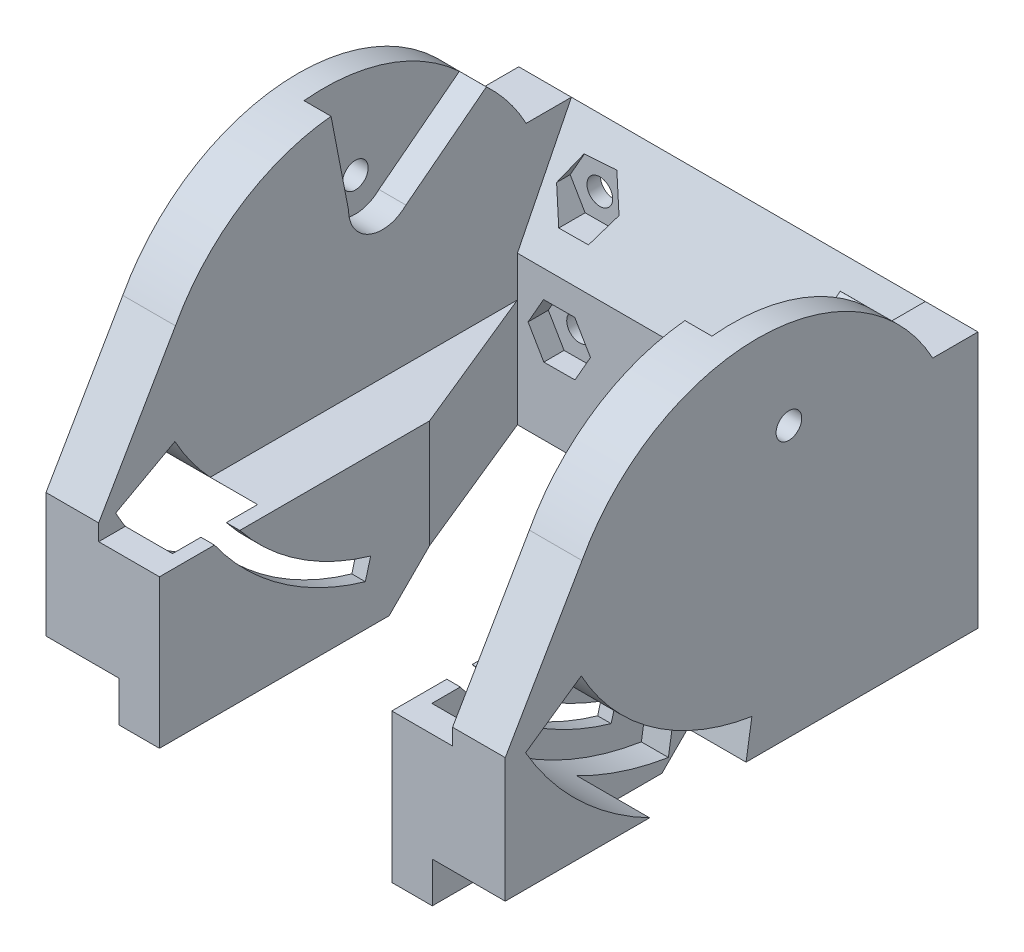
SolidWorks part; units mm, degrees
ref_plane "Alzado" through (0, 0, 0) normal (0, 0, 1) x (1, 0, 0)
ref_plane "Planta" through (0, 0, 0) normal (0, 1, 0) x (1, 0, 0)
ref_plane "Vista lateral" through (0, 0, 0) normal (1, 0, 0) x (0, 0, -1)
sketch "Croquis1" plane through (0, 0, 0) normal (0, 0, 1) x (1, 0, 0)
  line L1 (-48.8873, 14.6225) -> (-14.8873, 14.6225)
  line L2 (-48.8873, 14.6225) -> (-48.8873, -4.3775)
  line L3 (-48.8873, -4.3775) -> (-14.8873, -4.3775)
  line L4 (-14.8873, 14.6225) -> (-14.8873, -4.3775)
  dimension "D1" = 19
  dimension "D2" = 34
extrude "Saliente-Extruir1" add sketch "Croquis1" along normal blind 35
sketch "Croquis2" plane through (0, -4.3775, 0) normal (0, -1, 0) x (1, 0, 0)
  line L0 (-48.8873, 35) -> (-14.8873, 35) construction
  line L1 (-44.9873, 35) -> (-18.7873, 35)
  line L2 (-44.9873, 35) -> (-44.9873, 4)
  line L3 (-44.9873, 4) -> (-18.7873, 4)
  line L4 (-18.7873, 35) -> (-18.7873, 4)
  line L5 (-48.8873, 35) -> (-48.8873, 0) construction
  line L6 (-14.8873, 35) -> (-14.8873, 0) construction
  line L7 (-48.8873, 0) -> (-14.8873, 0) construction
  dimension "D1" = 3.9
  dimension "D2" = 3.9
  dimension "D3" = 26.2
  dimension "D4" = 4
extrude "Cortar-Extruir1" cut sketch "Croquis2" against normal blind 25
sketch "Croquis4" plane through (-18.7873, 0, 0) normal (-1, 0, 0) x (0, 0, 1)
  line L0 (4, 14.6225) -> (4, 6.6225)
  line L1 (4, 14.6225) -> (4, -4.3775) construction
  line L2 (4, 6.6225) -> (0, 14.6225)
  line L3 (0, 14.6225) -> (4, 14.6225)
extrude "Cortar-Extruir3" cut sketch "Croquis4" along normal up to vertex (26.2 mm away) up to point (-44.9873, 14.6225, 4)
sketch "Croquis9" plane through (-14.8873, 0, 0) normal (1, 0, 0) x (0, 0, -1)
  line L0 (-35, 14.6225) -> (0, 14.6225) construction
  line L1 (-29.3158, 14.6225) -> (-3.3495, 14.6225)
  line L7 (-35, -4.3775) -> (0, -4.3775) construction
  arc A0 (-29.3158, 14.6225) -> (-3.3495, 14.6225) centre (-16.3327, 7.6225) cw
  dimension "D2" = 12
extrude "Saliente-Extruir2" add sketch "Croquis9" against normal up to vertex (34 mm away) up to point (-48.8873, 14.6225, 35)
sketch "Croquis10" plane through (0, 14.6225, 0) normal (0, -1, 0) x (1, 0, 0)
  line L1 (-44.9873, 29.3158) -> (-18.7873, 29.3158)
  line L2 (-44.9873, 29.3158) -> (-44.9873, 3.3495)
  line L3 (-44.9873, 3.3495) -> (-18.7873, 3.3495)
  line L4 (-18.7873, 29.3158) -> (-18.7873, 3.3495)
extrude "Cortar-Extruir4" cut sketch "Croquis10" against normal blind 10
sketch "Croquis18" plane through (0, 0, 0) normal (0, 0, -1) x (-1, 0, 0)
  line L0 (48.8873, -4.3775) -> (14.8873, -4.3775) construction
  line L2 (48.8873, 14.6225) -> (48.8873, -4.3775) construction
  circle A0 centre (41.8873, 2.6225) radius 0.95
  circle A1 centre (21.8873, 2.6225) radius 0.95
  circle A2 centre (21.8873, 10.6225) radius 0.95
  circle A3 centre (41.8873, 10.6225) radius 0.95
  dimension "D1" = 7
  dimension "D2" = 7
  dimension "D3" = 2
  dimension "D4" = 2
extrude "Cortar-Extruir11" cut sketch "Croquis18" against normal up to vertex (4 mm away) up to point (-18.7873, -4.3775, 4)
sketch "Croquis19" plane through (0, 0, 4) normal (0, 0, 1) x (1, 0, 0)
  line L0 (-43.0308, 0.6161) -> (-40.7214, 0.629)
  line L1 (-23.0308, 0.6161) -> (-20.7214, 0.629)
  line L2 (-20.7214, 0.629) -> (-19.5779, 2.6355)
  line L3 (-19.5779, 2.6355) -> (-20.7438, 4.629)
  line L4 (-20.7438, 4.629) -> (-23.0531, 4.6161)
  line L5 (-23.0531, 4.6161) -> (-24.1966, 2.6096)
  line L6 (-24.1966, 2.6096) -> (-23.0308, 0.6161)
  line L7 (-40.7214, 0.629) -> (-39.5779, 2.6355)
  line L8 (-39.5779, 2.6355) -> (-40.7438, 4.629)
  line L9 (-40.7438, 4.629) -> (-43.0531, 4.6161)
  line L10 (-43.0531, 4.6161) -> (-44.1966, 2.6096)
  line L11 (-44.1966, 2.6096) -> (-43.0308, 0.6161)
  circle A0 centre (-21.8873, 2.6225) radius 2 construction
  circle A1 centre (-41.8873, 2.6225) radius 2 construction
  dimension "D1" = 4
  dimension "D2" = 2
extrude "Cortar-Extruir12" cut sketch "Croquis19" against normal blind 1.5
sketch "Croquis20" plane through (0, 0, 4) normal (0, 0, 1) x (1, 0, 0)
  line L12 (-44.0812, 10.6103) -> (-42.9736, 8.7165)
  line L13 (-42.9736, 8.7165) -> (-40.7797, 8.7287)
  line L14 (-40.7797, 8.7287) -> (-39.5207, 10.7358)
  line L15 (-39.5207, 10.7358) -> (-40.6283, 12.6296)
  line L16 (-40.6283, 12.6296) -> (-42.9948, 12.5164)
  line L17 (-42.9948, 12.5164) -> (-44.0812, 10.6103)
  line L18 (-24.0812, 10.6103) -> (-22.9736, 8.7165)
  line L19 (-22.9736, 8.7165) -> (-20.7797, 8.7287)
  line L20 (-20.7797, 8.7287) -> (-19.5207, 10.7358)
  line L21 (-19.5207, 10.7358) -> (-20.6283, 12.6296)
  line L22 (-20.6283, 12.6296) -> (-22.9948, 12.5164)
  line L23 (-22.9948, 12.5164) -> (-24.0812, 10.6103)
  circle A2 centre (-41.8873, 10.6225) radius 1.9 construction
  circle A3 centre (-21.8873, 10.6225) radius 1.9 construction
  dimension "D1" = 4
  dimension "D2" = 4
extrude "Cortar-Extruir13" cut sketch "Croquis20" against normal blind 3
sketch "Croquis21" plane through (-14.8873, 0, 0) normal (1, 0, 0) x (0, 0, -1)
  line L0 (0, -4.3775) -> (0, 14.6225) construction
  line L2 (-35, -4.3775) -> (0, -4.3775) construction
  circle A0 centre (-14, 15.6225) radius 0.95
  dimension "D1" = 14
  dimension "D2" = 20
extrude "Cortar-Extruir14" cut sketch "Croquis21" against normal up to vertex (34 mm away) up to point (-48.8873, 14.6225, 3.3495)
sketch "Croquis23" plane through (0, -4.3775, 0) normal (0, -1, 0) x (1, 0, 0)
  line L0 (-44.9873, 35) -> (-40.4873, 35)
  line L1 (-40.4873, 35) -> (-40.4873, 15)
  line L2 (-40.4873, 15) -> (-44.9873, 4)
  line L3 (-44.9873, 35) -> (-44.9873, 4) construction
  line L4 (-44.9873, 4) -> (-44.9873, 35)
  line L5 (-18.7873, 35) -> (-23.2873, 35)
  line L6 (-23.2873, 35) -> (-23.2873, 15)
  line L7 (-23.2873, 15) -> (-18.7873, 4)
  line L8 (-18.7873, 4) -> (-18.7873, 35)
extrude "Saliente-Extruir3" add sketch "Croquis23" against normal blind 8
sketch "Croquis24" plane through (-14.8873, 0, 0) normal (1, 0, 0) x (0, 0, -1)
  line L5 (-19.3648, -2.8648) -> (-19.7593, -4.312)
  line L6 (-30.433, 5.5966) -> (-31.6653, 4.7372)
  arc A0 (-19.3648, -2.8648) -> (-30.433, 5.5966) centre (-14, 15.6225) cw
  arc A1 (-31.6653, 4.7372) -> (-19.7593, -4.312) centre (-14, 15.6225) ccw
  dimension "D1" = 1.5
  dimension "D2" = 19.25
  dimension "D3" = 20.7498
extrude "Cortar-Extruir16" cut sketch "Croquis24" against normal up to vertex (34 mm away) up to point (-48.8873, -4.3775, 35)
sketch "Croquis25" plane through (0, -4.3775, 0) normal (0, -1, 0) x (1, 0, 0)
  line L1 (-23.2873, 35) -> (-20.2873, 35)
  line L2 (-23.2873, 35) -> (-23.2873, 15)
  line L3 (-23.2873, 15) -> (-20.2873, 15)
  line L4 (-20.2873, 35) -> (-20.2873, 15)
  line L5 (-40.4873, 35) -> (-43.4873, 35)
  line L6 (-40.4873, 35) -> (-40.4873, 15)
  line L7 (-40.4873, 15) -> (-43.4873, 15)
  line L8 (-43.4873, 35) -> (-43.4873, 15)
  dimension "D1" = 3
  dimension "D2" = 3
extrude "Saliente-Extruir4" add sketch "Croquis25" along normal blind 3
sketch "Croquis26" plane through (-20.2873, 0, 0) normal (1, 0, 0) x (0, 0, -1)
  line L0 (-18, -7.3775) -> (-15, -7.3775)
  line L2 (-15, -7.3775) -> (-15, -4.3775)
  line L3 (-15, -7.3775) -> (-35, -7.3775) construction
  line L4 (-18, -7.3775) -> (-15, -4.3775)
extrude "Cortar-Extruir17" cut sketch "Croquis26" against normal up to vertex (23.2 mm away) up to point (-43.4873, -7.3775, 15)
sketch "Croquis27" plane through (-14.8873, 0, 0) normal (1, 0, 0) x (0, 0, -1)
  line L4 (-16.7403, -1.6616) -> (-17.5233, -6.5999)
  line L6 (-29.3712, 7.2574) -> (-33.492, 4.3837)
  arc A0 (-29.3712, 7.2574) -> (-16.7403, -1.6616) centre (-14, 15.6225) ccw
  arc A1 (-33.492, 4.3837) -> (-17.5233, -6.5999) centre (-14, 15.6225) ccw
extrude "Cortar-Extruir18" cut sketch "Croquis27" against normal blind 7.4
sketch "Croquis28" plane through (-48.8873, 0, 0) normal (-1, 0, 0) x (0, 0, 1)
  line L4 (29.3544, 7.2266) -> (33.7414, 4.8278)
  line L5 (16.7546, -1.6593) -> (17.5416, -6.597)
  arc A0 (29.3544, 7.2266) -> (16.7546, -1.6593) centre (14, 15.6225) cw
  arc A1 (33.7414, 4.8278) -> (17.5416, -6.597) centre (14, 15.6225) cw
extrude "Cortar-Extruir19" cut sketch "Croquis28" against normal blind 7.4
sketch "Croquis29" plane through (-18.7873, 0, 0) normal (-1, 0, 0) x (0, 0, 1)
  line L0 (17.7974, 22.2996) -> (16.5, 15.6225)
  line L1 (6.2969, 18.4321) -> (12.2534, 13.8338)
  arc A0 (6.2969, 18.4321) -> (17.7974, 22.2996) centre (16.3327, 7.6225) cw
  arc A1 (29.3158, 14.6225) -> (3.3495, 14.6225) centre (16.3327, 7.6225) ccw construction
  arc A2 (16.5, 15.6225) -> (12.2534, 13.8338) centre (14, 15.6225) cw
extrude "Cortar-Extruir20" cut sketch "Croquis29" against normal blind 2
extrude "Cortar-Extruir21" cut sketch "Croquis29<2>" along normal blind 28.2
sketch "Croquis29<2>" plane through (-18.7873, 0, 0) normal (-1, 0, 0) x (0, 0, 1) same geometry as "Croquis29"
sketch "Croquis30" plane through (-48.8873, 0, 0) normal (-1, 0, 0) x (0, 0, 1)
  line L0 (29.3158, 14.6225) -> (35, 4.8278)
  line L1 (35, 14.6225) -> (35, -4.3775) construction
  line L2 (35, 4.8278) -> (35, 14.6225)
  line L3 (35, 14.6225) -> (29.3158, 14.6225)
extrude "Cortar-Extruir22" cut sketch "Croquis30" against normal up to vertex (34 mm away) up to point (-14.8873, 14.6225, 35)
